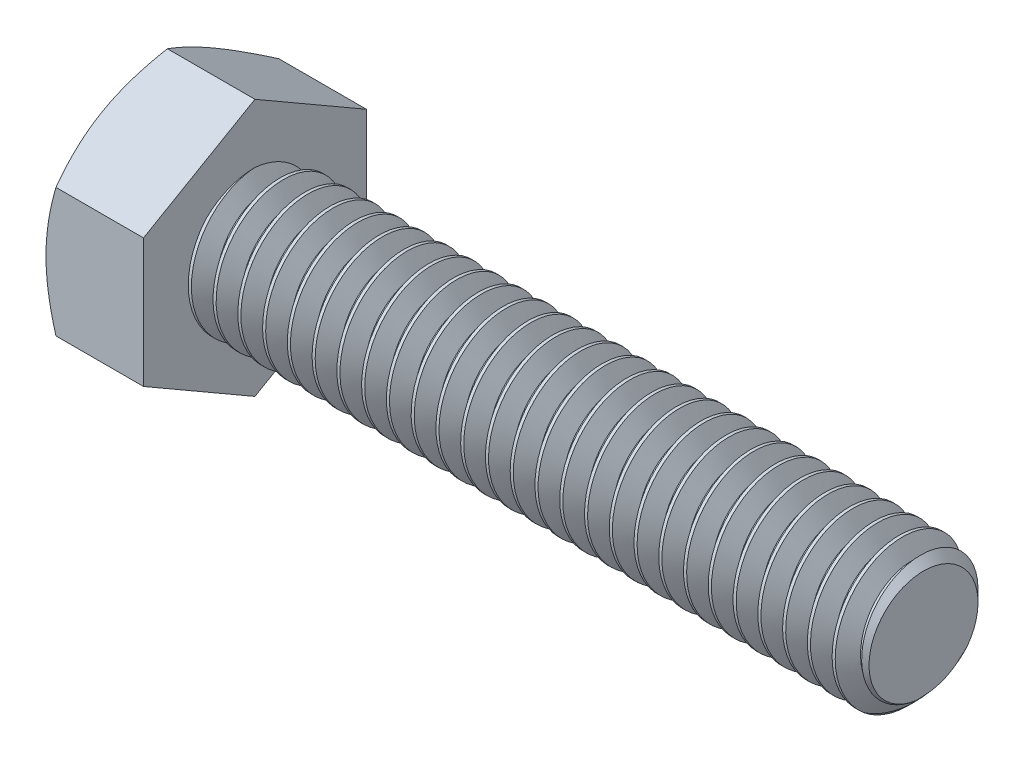
SolidWorks part; units mm, degrees
ref_plane "Front Plane" through (0, 0, 0) normal (0, 0, 1) x (1, 0, 0)
ref_plane "Top Plane" through (0, 0, 0) normal (0, 1, 0) x (1, 0, 0)
ref_plane "Right Plane" through (0, 0, 0) normal (1, 0, 0) x (0, 0, -1)
sketch "Sketch1" plane through (0, 0, 0) normal (0, 0, 1) x (1, 0, 0)
  line L0 (-21.8281, 0) -> (21.8281, 0) construction
  line L1 (21.8281, 3.9688) -> (21.8281, -3.9688) construction
  line L2 (-16.2719, 6.35) -> (-16.2719, -6.35) construction
  line L3 (-21.8281, 6.35) -> (-21.8281, -6.35) construction
  point P9 (-16.2719, 0)
  point P10 (16.8892, -3.9688)
  dimension "Screw Dia" = 7.9375
  dimension "Hex" = 12.7
  dimension "Head Ht" = 5.5562
  dimension "Screw Lenght" = 38.1
  dimension "D1" = 4.9389
ref_plane "Plane2" through (21.8281, 0, 0) normal (1, 0, 0) x (0, 0, -1)
sketch "Sketch5" plane through (21.8281, 0, 0) normal (1, 0, 0) x (0, 0, -1)
  circle A0 centre (0, 0) radius 3.9688
extrude "Boss-Extrude3" add sketch "Sketch5" against normal up to vertex (38.1 mm away) up to point (-16.2719, 0, 0)
sketch "Sketch9" plane through (21.8281, 0, 0) normal (1, 0, 0) x (0, 0, -1)
  circle A1 centre (0, 0) radius 3.9688
  circle A2 centre (0, 0) radius 3.9688
  dimension "D1" = 0
curve "Helix/Spiral1" pitch 1.4111 height 39.5111 turns 28 parameters "Pitch"=1.4111
chamfer "Chamfer1" distance 0.8636 angle 45 1 edges at (21.8281, 0, -3.9688)
sketch "Sketch10" plane through (0, 0, 0) normal (0, 0, 1) x (1, 0, 0)
  line L0 (21.8281, 3.9688) -> (22.3573, 3.0522)
  line L1 (22.3573, 3.0522) -> (22.5337, 3.0522)
  line L2 (22.5337, 3.0522) -> (23.0628, 3.9687)
  line L3 (21.8281, 3.9688) -> (23.0628, 3.9687)
  line L4 (22.4455, 3.9688) -> (22.4455, 3.0522) construction
  line L5 (22.0927, 3.5105) -> (22.7983, 3.5105) construction
  dimension "D1" = 60
  dimension "D2" = 0.1764
  dimension "D3" = 0.7056
sweep "Cut-Sweep1" cut profiles "Sketch10" path "Helix/Spiral1"
sketch "Sketch6" plane through (-16.2719, 0, 0) normal (-1, 0, 0) x (0, 0, 1)
  line L0 (0, 6.35) -> (0, -6.35) construction
  line L1 (6.35, 3.6662) -> (0, 7.3323)
  line L2 (0, 7.3323) -> (-6.35, 3.6662)
  line L3 (-6.35, 3.6662) -> (-6.35, -3.6662)
  line L4 (-6.35, -3.6662) -> (0, -7.3323)
  line L5 (0, -7.3323) -> (6.35, -3.6662)
  line L6 (6.35, -3.6662) -> (6.35, 3.6662)
  circle A0 centre (0, 0) radius 6.35 construction
extrude "Boss-Extrude4" add sketch "Sketch6" along normal up to vertex (5.5563 mm away) up to point (-21.8281, -6.35, 0)
sketch "Sketch7" plane through (-21.8281, 0, 0) normal (-1, 0, 0) x (0, 0, 1)
  circle A0 centre (0, 0) radius 6.35 construction
  circle A1 centre (0, 0) radius 6.35
sketch "Sketch8" plane through (-21.8281, 0, 0) normal (-1, 0, 0) x (0, 0, 1)
  circle A0 centre (0, 0) radius 6.35 construction
  circle A1 centre (0, 0) radius 6.35
extrude "Cut-Extrude3" cut sketch "Sketch8" against normal through all draft 60 flip side to cut
sketch "Sketch12" plane through (-21.8281, 0, 0) normal (-1, 0, 0) x (0, 0, 1)
  line L0 (0, 4.8895) -> (0, 2.7305) construction
  line L1 (0.1905, 4.8895) -> (0.1905, 2.7305)
  line L2 (-0.1905, 4.8895) -> (-0.1905, 2.7305)
  line L3 (0, 3.9688) -> (0, -3.9688) construction
  arc A0 (0.1905, 4.8895) -> (-0.1905, 4.8895) centre (0, 4.8895) ccw
  arc A1 (-0.1905, 2.7305) -> (0.1905, 2.7305) centre (0, 2.7305) ccw
  circle A3 centre (0, 0) radius 2.54 construction
  circle A4 centre (0, 0) radius 5.08 construction
  point P2 (0, 3.81)
  dimension "D1" = 5.08
  dimension "D3" = 10.16
  dimension "D2" = 0.381
extrude "Cut-Extrude4" cut sketch "Sketch12" against normal blind 0.254
pattern_circular "CirPattern1" count 3 over 360 about axis through (0, 0, 0) along (1, 0, 0) of "Cut-Extrude4"
equation "\"D2@Sketch10\" = \"Pitch@Helix/Spiral1\"*.125"
equation "\"D3@Sketch10\" = \"Pitch@Helix/Spiral1\"*.5"
equation "\"D1@Chamfer1\" = \"Pitch@Helix/Spiral1\"*.612"
equation "\"D1@Sketch12\" = \"Hex@Sketch1\"*.4"
equation "\"D3@Sketch12\" = \"Hex@Sketch1\"*.8"
equation "\"D2@Sketch12\" = \"Hex@Sketch1\"*.03"
equation "\"D1@Sketch1\" = \"Pitch@Helix/Spiral1\"*3.5"
equation "\"D3@Helix/Spiral1\" = \"Screw Lenght@Sketch1\"+\"Pitch@Helix/Spiral1\""
